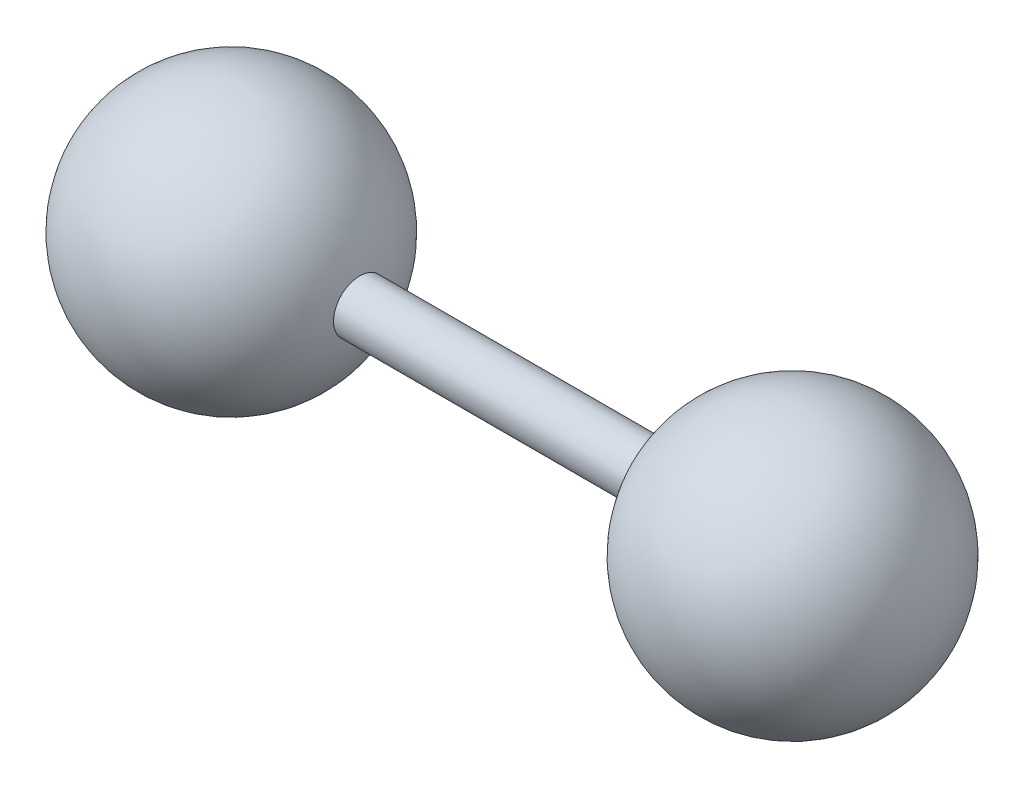
SolidWorks part; units mm, degrees
ref_plane "Front Plane" through (0, 0, 0) normal (0, 0, 1) x (1, 0, 0)
ref_plane "Top Plane" through (0, 0, 0) normal (0, 1, 0) x (1, 0, 0)
ref_plane "Right Plane" through (0, 0, 0) normal (1, 0, 0) x (0, 0, -1)
sketch "Sketch1" plane through (0, 0, 0) normal (0, 0, 1) x (1, 0, 0)
  line L0 (0, 0) -> (1501.0726, 0)
  arc A0 (0, 0) -> (1501.0726, 0) centre (750.5363, 0) cw
revolve "Revolve1" add sketch "Sketch1" angle 360 about L0
sketch "Sketch3" plane through (0, 0, 0) normal (1, 0, 0) x (0, 0, -1)
  circle A0 centre (0, 0) radius 150
extrude "Boss-Extrude1" add sketch "Sketch3" along normal blind 650 and the other way blind 1800
sketch "Sketch4" plane through (0, 0, 0) normal (0, 0, 1) x (1, 0, 0)
  line L2 (-1710.6036, 0) -> (-3210.6036, 0)
  arc A3 (-1710.6036, 0) -> (-3210.6036, 0) centre (-2460.6036, 0) ccw
revolve "Revolve2" add sketch "Sketch4" angle 360 about L2
sketch "Sketch5" plane through (0, 0, 0) normal (0, 0, 1) x (1, 0, 0)
  point P5 (-2460.6036, 0)
  point P6 (750.5363, 0)
scale "Scale1" scale about centroid uniform scaling yes scale factor 0.5
